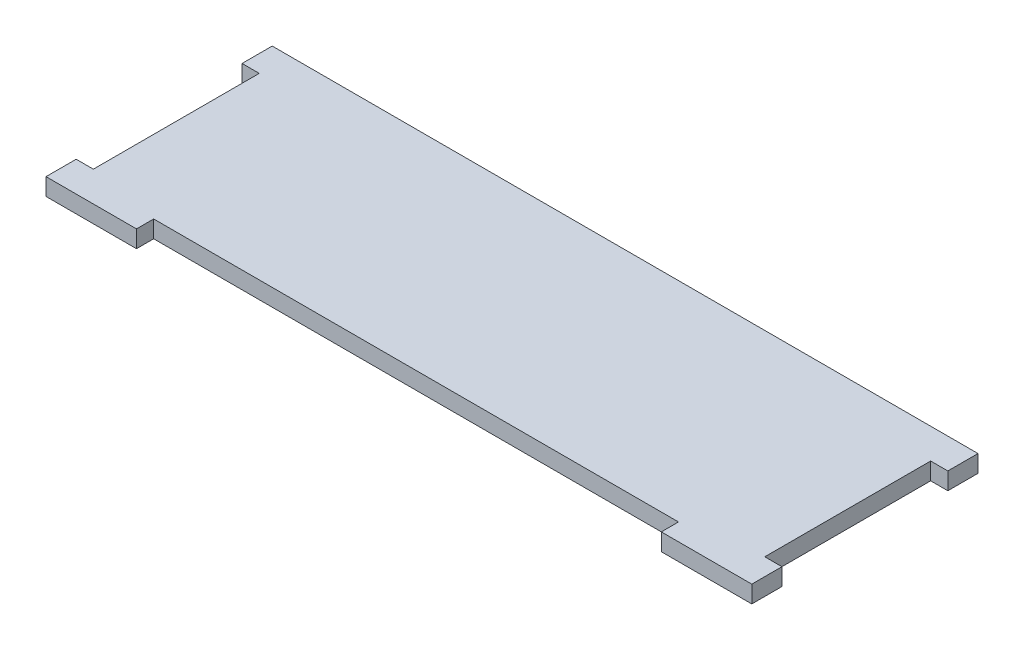
SolidWorks part; units mm, degrees
ref_plane "Front Plane" through (0, 0, 0) normal (0, 0, 1) x (1, 0, 0)
ref_plane "Top Plane" through (0, 0, 0) normal (0, 1, 0) x (1, 0, 0)
ref_plane "Right Plane" through (0, 0, 0) normal (1, 0, 0) x (0, 0, -1)
sketch "Sketch1" plane through (0, 0, 0) normal (0, 1, 0) x (1, 0, 0)
  line L1 (0, 0) -> (234, 0)
  line L2 (0, 0) -> (0, 75)
  line L3 (0, 75) -> (234, 75)
  line L4 (234, 0) -> (234, 75)
  dimension "D1" = 234
  dimension "D2" = 75
extrude "Boss-Extrude1" add sketch "Sketch1" along normal blind 5.7
sketch "Sketch2" plane through (0, 5.7, 0) normal (0, 1, 0) x (1, 0, 0)
  line L0 (0, 75) -> (0, 0) construction
  line L1 (0, 65) -> (5.7, 65)
  line L2 (0, 65) -> (0, 10)
  line L3 (0, 10) -> (5.7, 10)
  line L4 (5.7, 65) -> (5.7, 10)
  line L5 (0, 0) -> (234, 0) construction
  line L6 (234, 75) -> (0, 75) construction
  line L7 (234, 0) -> (234, 75) construction
  line L8 (234, 65) -> (228.3, 65)
  line L9 (234, 65) -> (234, 10)
  line L10 (234, 10) -> (228.3, 10)
  line L11 (228.3, 65) -> (228.3, 10)
  dimension "D1" = 10
  dimension "D2" = 10
  dimension "D3" = 5.7
  dimension "D4" = 10
  dimension "D5" = 10
  dimension "D6" = 5.7
extrude "Cut-Extrude1" cut sketch "Sketch2" against normal blind 5.7
sketch "Sketch3" plane through (0, 5.7, 0) normal (0, 1, 0) x (1, 0, 0)
  line L0 (0, 0) -> (234, 0) construction
  line L1 (30, 0) -> (204, 0)
  line L2 (30, 0) -> (30, 5.7)
  line L3 (30, 5.7) -> (204, 5.7)
  line L4 (204, 0) -> (204, 5.7)
  line L5 (0, 10) -> (0, 0) construction
  line L6 (234, 0) -> (234, 10) construction
  dimension "D1" = 30
  dimension "D2" = 30
  dimension "D3" = 5.7
extrude "Cut-Extrude2" cut sketch "Sketch3" against normal blind 5.7
